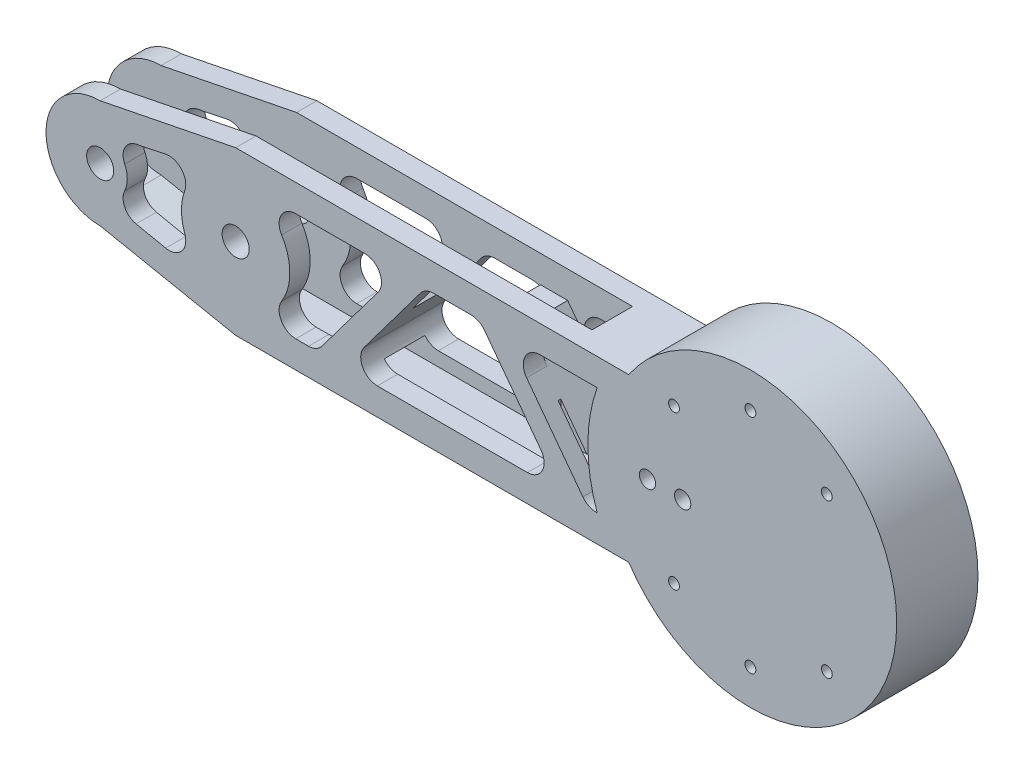
SolidWorks part; units mm, degrees
ref_plane "前视基准面" through (0, 0, 0) normal (0, 0, 1) x (1, 0, 0)
ref_plane "上视基准面" through (0, 0, 0) normal (0, 1, 0) x (1, 0, 0)
ref_plane "右视基准面" through (0, 0, 0) normal (1, 0, 0) x (0, 0, -1)
sketch "草图1" plane through (0, 0, 0) normal (1, 0, 0) x (0, 0, -1)
  line L0 (7.5, 0) -> (7.5, 15)
  line L11 (7.5, 15) -> (-7.5, 15)
  line L12 (-7.5, 15) -> (-7.5, -15)
  line L13 (-7.5, -15) -> (7.5, -15)
  line L14 (7.5, -15) -> (7.5, 0)
  dimension "D1" = 15
  dimension "D2" = 15
  dimension "D3" = 30
  dimension "D4" = 15
extrude "凸台-拉伸1" add sketch "草图1" along normal blind 60 and the other way blind 70
sketch "草图2" plane through (0, 0, 0) normal (0, 0, 1) x (1, 0, 0)
  line L2 (60, 15) -> (60, -15) construction
  circle A4 centre (60, 0) radius 27
  circle A5 centre (60, 0) radius 23.5
  dimension "D2" = 47
  dimension "D1" = 54
extrude "凸台-拉伸2" add sketch "草图2" along normal blind 7.5 and the other way blind 7.5
sketch "草图3" plane through (0, 0, 0) normal (0, 0, 1) x (1, 0, 0)
  line L0 (60, 15) -> (60, -15) construction
  circle A0 centre (60, 0) radius 24.5
  dimension "D1" = 49
extrude "切除-拉伸1" cut sketch "草图3" against normal blind 7.5 and the other way blind 7.5
sketch "草图4" plane through (0, 0, 7.5) normal (0, 0, 1) x (1, 0, 0)
  circle A1 centre (60, 0) radius 24.5
  dimension "D1" = 49
extrude "凸台-拉伸3" add sketch "草图4" against normal blind 3
sketch "草图5" plane through (0, 0, 4.5) normal (0, 0, -1) x (-1, 0, 0)
  line L0 (-36.5, 0) -> (-57.3178, 0) construction
  line L1 (-36.5, 0) -> (-36.5, 4)
  line L2 (-36.5, 4) -> (-40.5, 4)
  line L3 (-40.5, 4) -> (-45.5, 4)
  line L5 (-50.5, 0) -> (-50.5, 4)
  line L6 (-50.5, 4) -> (-45.5, 4)
  line L7 (-50.5, 0) -> (-50.5, -4)
  line L8 (-50.5, -4) -> (-36.5, -4)
  line L9 (-36.5, -4) -> (-36.5, 0)
  dimension "D1" = 4
  dimension "D2" = 4
  dimension "D3" = 5
  dimension "D4" = 14
  dimension "D5" = 4
extrude "凸台-拉伸4" add sketch "草图5" along normal blind 2.58
sketch "草图6" plane through (0, 0, 4.5) normal (0, 0, -1) x (-1, 0, 0)
  line L0 (-60, 29.757) -> (-60, -28.858) construction
  line L1 (-93.4216, 0) -> (-30.7153, 0) construction
  circle A0 centre (-60, 0) radius 20.5 construction
  circle A1 centre (-60, 20.5) radius 1
  circle A5 centre (-60, -20.5) radius 1
  circle A9 centre (-80.5, 0) radius 1 [skipped]
  circle A10 centre (-39.5, 0) radius 1 [skipped]
  circle A11 centre (-45.5043, 14.4957) radius 1 [skipped]
  circle A12 centre (-74.4957, 14.4957) radius 1 [skipped]
  circle A13 centre (-74.4957, -14.4957) radius 1 [skipped]
  circle A14 centre (-45.5043, -14.4957) radius 1 [skipped]
  circle A15 centre (-60, 0) radius 20 construction
  circle A16 centre (-45.8949, 14.1791) radius 1
  circle A17 centre (-74.1051, 14.1791) radius 1
  circle A18 centre (-74.1051, -14.1791) radius 1
  circle A19 centre (-45.8949, -14.1791) radius 1
  point P28 (-60, 0)
  dimension "D1" = 41
  dimension "D2" = 2
  dimension "D4" = 40
  dimension "D6" = 2
  dimension "D3" = 8
extrude "切除-拉伸2" cut sketch "草图6" against normal blind 3
sketch "草图7" plane through (0, 0, 1.92) normal (0, 0, -1) x (-1, 0, 0)
  circle A0 centre (-47.5, 0) radius 1.5
  circle A1 centre (-41, 0) radius 1.5
  dimension "D2" = 3
  dimension "D4" = 3
extrude "切除-拉伸3" cut sketch "草图7" against normal blind 5.58
sketch "草图8" plane through (-70, 0, 0) normal (-1, 0, 0) x (0, 0, 1)
  line L1 (-7.5, 15) -> (7.5, 15) construction
  line L2 (0, 15) -> (-3.75, 15)
  line L3 (-7.5, 15) -> (7.5, 15) construction
  line L4 (-3.75, 15) -> (-3.75, -15)
  line L5 (7.5, -15) -> (-7.5, -15) construction
  line L6 (-3.75, -15) -> (3.75, -15)
  line L7 (7.5, -15) -> (-7.5, -15) construction
  line L8 (3.75, -15) -> (3.75, 15)
  line L9 (3.75, 15) -> (0, 15)
  dimension "D1" = 3.75
  dimension "D2" = 7.5
extrude "切除-拉伸4" cut sketch "草图8" against normal blind 97
ref_plane "基准面1" through (36.5, 0, 0) normal (1, 0, 0) x (0, 0, -1)
sketch "草图9" plane through (36.5, 0, 0) normal (1, 0, 0) x (0, 0, -1)
  line L9 (3.75, 0) -> (3.75, 9.1)
  line L10 (3.75, 0) -> (3.75, 9.1)
  line L11 (3.75, 9.1) -> (-4.5, 9.1)
  line L12 (-4.5, 9.1) -> (-4.5, -9.1)
  line L13 (3.75, 0) -> (3.75, -9.1)
  line L14 (3.75, -9.1) -> (-4.5, -9.1)
  dimension "D1" = 9.1
  dimension "D2" = 8.25
  dimension "D3" = 18.2
  dimension "D4" = 9.1
extrude "切除-拉伸5" cut sketch "草图9" against normal blind 15 and the other way blind 1 contours L14 L13 L9 L11 L12 region at (36.5, 0, 0.375)
sketch "草图10" plane through (0, 0, 0) normal (0, 0, 1) x (1, 0, 0)
  line L0 (0, 0) -> (-60, 0) construction
  line L1 (-60, 0) -> (-35, 0) construction
  line L2 (-35, 15) -> (-60, 10)
  line L3 (-70, 15) -> (37.5501, 15) construction
  line L4 (-60, 0) -> (-70, 0) construction
  line L5 (-35, -15) -> (-60, -10)
  line L6 (-53.3819, 6.3701) -> (-47.9103, 7.5028)
  line L7 (-53.3819, -6.3701) -> (-47.9103, -7.5028)
  line L8 (-35, 10) -> (35, 10) construction
  line L9 (-35, -10) -> (35, -10) construction
  line L10 (-23.901, 10) -> (-11.1594, 10)
  line L12 (-23.901, -10) -> (-21.5399, -10)
  line L13 (-19.0761, -8.7681) -> (-8.6957, 5.0725)
  line L14 (-5, 10) -> (0, 10) construction
  line L15 (-20, -10) -> (-15, -10) construction
  line L16 (-11.3043, -5.0725) -> (-0.9239, 8.7681)
  line L17 (1.5399, 10) -> (8.4601, 10)
  line L18 (5, 12.2067) -> (5, -12.3113)
  line L19 (-8.8406, -10) -> (5, -10)
  line L20 (5, -10) -> (18.8406, -10)
  line L21 (21.3043, -5.0725) -> (10.9239, 8.7681)
  line L22 (10, 10) -> (15, 10) construction
  line L23 (18.6957, 5.0725) -> (29.0761, -8.7681)
  line L24 (31.5399, -10) -> (31.7157, -10)
  line L25 (21.1594, 10) -> (31.7157, 10)
  line L27 (-35, 15) -> (-70, 15)
  line L28 (-70, 15) -> (-70, -15) construction
  line L29 (-70, 15) -> (-70, -15)
  line L30 (-70, -15) -> (-35, -15)
  circle A0 centre (-60, 0) radius 2.5
  circle A1 centre (-35, 0) radius 2.5
  arc A6 (-60, -10) -> (-60, 10) centre (-60, 0) cw
  arc A7 (-55.4836, 2.1452) -> (-55.4836, -2.1452) centre (-60, 0) cw
  arc A8 (-44.3932, 3.4305) -> (-44.3932, -3.4305) centre (-35, 0) ccw
  arc A10 (-26.5143, 5.2909) -> (-26.5143, -5.2909) centre (-35, 0) cw
  arc A11 (-55.4836, 2.1452) -> (-53.3819, 6.3701) centre (-52.7737, 3.4323) cw
  arc A12 (-53.3819, -6.3701) -> (-55.4836, -2.1452) centre (-52.7737, -3.4323) cw
  arc A13 (-44.3932, 3.4305) -> (-47.9103, 7.5028) centre (-47.286, 4.487) ccw
  arc A14 (-47.9103, -7.5028) -> (-44.3932, -3.4305) centre (-47.286, -4.487) ccw
  arc A15 (-26.5143, 5.2909) -> (-23.901, 10) centre (-23.901, 6.9203) cw
  arc A16 (-23.901, -10) -> (-26.5143, -5.2909) centre (-23.901, -6.9203) cw
  arc A17 (-11.1594, 10) -> (-8.6957, 5.0725) centre (-11.1594, 6.9203) cw
  arc A18 (-21.5399, -10) -> (-19.0761, -8.7681) centre (-21.5399, -6.9203) ccw
  arc A19 (-8.8406, -10) -> (-11.3043, -5.0725) centre (-8.8406, -6.9203) cw
  arc A20 (1.5399, 10) -> (-0.9239, 8.7681) centre (1.5399, 6.9203) ccw
  arc A21 (10.9239, 8.7681) -> (8.4601, 10) centre (8.4601, 6.9203) ccw
  arc A22 (18.8406, -10) -> (21.3043, -5.0725) centre (18.8406, -6.9203) ccw
  arc A23 (18.6957, 5.0725) -> (21.1594, 10) centre (21.1594, 6.9203) cw
  arc A24 (31.5399, -10) -> (29.0761, -8.7681) centre (31.5399, -6.9203) cw
  arc A26 (31.7157, 10) -> (31.7157, -10) centre (60, 0) ccw
  point P45 (-60, 5)
  point P48 (-60, -5)
  point P51 (-37.8485, 9.5857)
  point P54 (-37.8485, -9.5857)
  point P77 (25, -10)
  point P83 (30, -10)
  dimension "D2" = 5
  dimension "D4" = 5
  dimension "D5" = 3
  dimension "D6" = 3
  dimension "D15" = 3.0797
  dimension "D16" = 3.0797
  dimension "D17" = 3.0797
  dimension "D8" = 3.0797
  dimension "D9" = 3.0797
  dimension "D18" = 3.0797
  dimension "D19" = 3.0797
  dimension "D20" = 3.0797
  dimension "D21" = 3.0797
  dimension "D22" = 3.0797
  dimension "D23" = 3.0797
  dimension "D24" = 3.0797
  dimension "D1" = 60
  dimension "D3" = 25
  dimension "D10" = 5
  dimension "D11" = 5
  dimension "D12" = 10
  dimension "D13" = 20
  dimension "D14" = 5
extrude "切除-拉伸6" cut sketch "草图10" against normal blind 7.5 and the other way through all contours L29 A6 L2 L27 | L5 A6 L29 L30 | A0 | L7 A14 A8 A13 L6 A11 A7 A12 | A1 | L12 A18 L13 A17 L10 A15 A10 A16 | L17 A20 L16 A19 L19 L18 | L20 A22 L21 A21 L17 L18 | A26 L25 A23 L23 A24 L24 region at (-59.2224, -12.1305, 0) region at (-59.2224, 12.1305, 0) region at (-49.8088, 0, 0) region at (-18.9131, 1.6478, 0) region at (-1.6337, -1.7794, 0) region at (11.6337, -1.7794, 0) region at (25.8146, 2.8144, 0) region at (-60, 0, 0) region at (-35, 0, 0)
sketch "草图11" plane through (0, 0, 0) normal (0, 0, 1) x (1, 0, 0)
  line L1 (-60, -7.5) -> (-34.5192, -12.5962)
  line L2 (-34.5192, -12.5962) -> (32.7725, -12.5962)
  line L3 (-35, -15) -> (37.5501, -15) construction
  line L4 (34.0192, -15) -> (-35, -15)
  line L5 (-35, -15) -> (-60, -10)
  line L7 (-65, -8.6603) -> (-63.75, -6.4952)
  arc A4 (32.7725, -12.5962) -> (34.0192, -15) centre (60, 0) ccw
  arc A5 (-63.75, -6.4952) -> (-60, -7.5) centre (-60, 0) ccw
  arc A6 (-60, -10) -> (-65, -8.6603) centre (-60, 0) cw
extrude "凸台-拉伸5" add sketch "草图11" along normal blind 4 and the other way blind 4
sketch "草图12" plane through (0, 0, 0) normal (0, 0, 1) x (1, 0, 0)
  line L1 (21.3043, -5.0725) -> (10.9239, 8.7681) construction
  line L2 (13.6957, 5.0725) -> (21.3043, -5.0725)
  line L3 (21.3043, -5.0725) -> (26.3043, -5.0725)
  line L4 (18.6957, 5.0725) -> (29.0761, -8.7681) construction
  line L5 (26.3043, -5.0725) -> (18.6957, 5.0725)
  line L6 (18.6957, 5.0725) -> (15.0186, 9.9752)
  line L7 (13.6957, 5.0725) -> (10.0186, 9.9752)
  line L8 (10.0186, 9.9752) -> (15.0186, 9.9752)
  line L9 (-19.0761, -8.7681) -> (-11.3043, -8.7681)
  line L11 (-11.3043, -5.0725) -> (-6.1141, 1.8478)
  line L12 (-11.3043, -5.0725) -> (-0.9239, 8.7681) construction
  line L13 (-6.1141, 1.8478) -> (-16.6379, -5.5173)
  line L14 (-19.0761, -8.7681) -> (-8.6957, 5.0725) construction
  line L15 (-16.6379, -5.5173) -> (-19.0761, -8.7681)
  arc A1 (-11.3043, -5.0725) -> (-8.8406, -10) centre (-8.8406, -6.9203) ccw construction
  arc A2 (-11.3043, -5.0725) -> (-11.3043, -8.7681) centre (-8.8406, -6.9203) ccw
extrude "凸台-拉伸6" add sketch "草图12" along normal blind 4 and the other way blind 4
